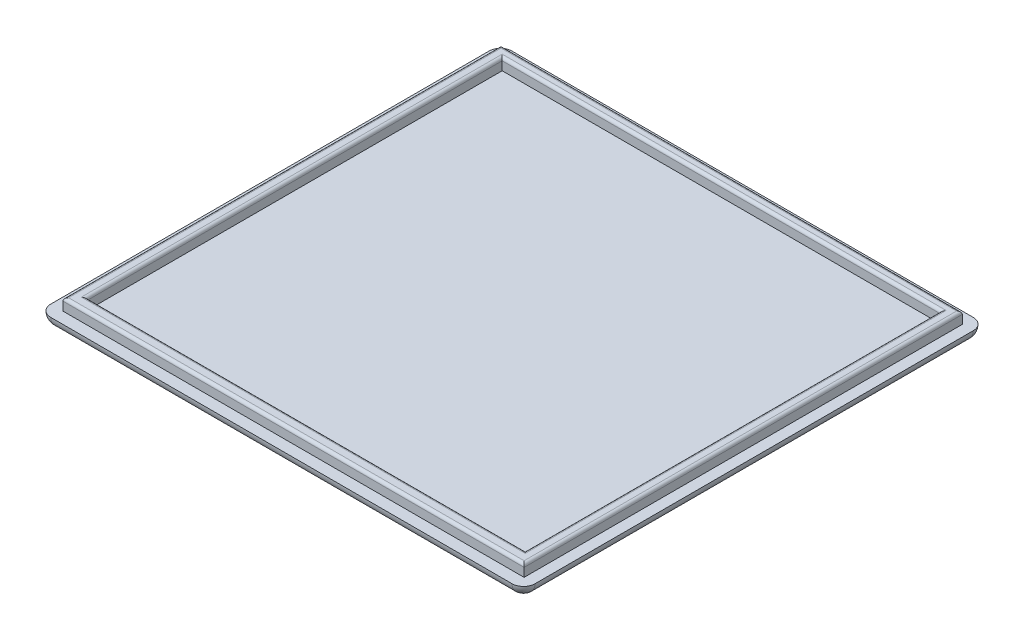
SolidWorks part; units mm, degrees
ref_plane "Front Plane" through (0, 0, 0) normal (0, 0, 1) x (1, 0, 0)
ref_plane "Top Plane" through (0, 0, 0) normal (0, 1, 0) x (1, 0, 0)
ref_plane "Right Plane" through (0, 0, 0) normal (1, 0, 0) x (0, 0, -1)
sketch "Sketch1" plane through (0, 0, 0) normal (0, 1, 0) x (1, 0, 0)
  line L1 (0, 0) -> (84, 0)
  line L2 (0, 0) -> (0, 80)
  line L3 (0, 80) -> (84, 80)
  line L4 (84, 0) -> (84, 80)
  dimension "D1" = 80
  dimension "D2" = 84
extrude "Boss-Extrude1" add sketch "Sketch1" along normal blind 2
sketch "Sketch3" plane through (0, 2, 0) normal (0, 1, 0) x (1, 0, 0)
  line L4 (2.1, 2) -> (82.1, 2)
  line L5 (2.1, 2) -> (2.1, 78)
  line L6 (2.1, 78) -> (82.1, 78)
  line L7 (82.1, 2) -> (82.1, 78)
  line L8 (2.1, 2) -> (82.1, 78) construction
  line L9 (2.1, 78) -> (82.1, 2) construction
  line L10 (4.1061, 4.1905) -> (80.1061, 4.1905)
  line L11 (4.1061, 4.1905) -> (4.1061, 76.1905)
  line L12 (4.1061, 76.1905) -> (80.1061, 76.1905)
  line L13 (80.1061, 4.1905) -> (80.1061, 76.1905)
  line L14 (4.1061, 4.1905) -> (80.1061, 76.1905) construction
  line L15 (4.1061, 76.1905) -> (80.1061, 4.1905) construction
  point P0 (0, 0)
  point P9 (42, 40)
  point P10 (42.1, 40)
  point P15 (42.1061, 40.1905)
  point P20 (2.1, 78)
  point P21 (4.2, 76)
  dimension "D1" = 76
  dimension "D2" = 72
  dimension "D3" = 76
  dimension "D4" = 80
extrude "Boss-Extrude2" add sketch "Sketch3" along normal blind 2 from surface starting at face at (42, 2, -40)
fillet "Fillet1" radius 2 4 edges at (84, 1, -80) (84, 1, 0) (0, 1, 0) (0, 1, -80)
fillet "Fillet2" radius 2 8 edges at (0.5858, 0, -0.5858) (0.5858, 0, -79.4142) (83.4142, 0, -79.4142) (83.4142, 0, -0.5858) (84, 0, -40) (42, 0, -80) (0, 0, -40) (42, 0, 0)
fillet "Fillet3" radius 0.5 8 edges at (42.1, 4, -2) (42.1061, 4, -4.1905) (80.1061, 4, -40.1905) (82.1, 4, -40) (42.1061, 4, -76.1905) (42.1, 4, -78) (2.1, 4, -40) (4.1061, 4, -40.1905)
